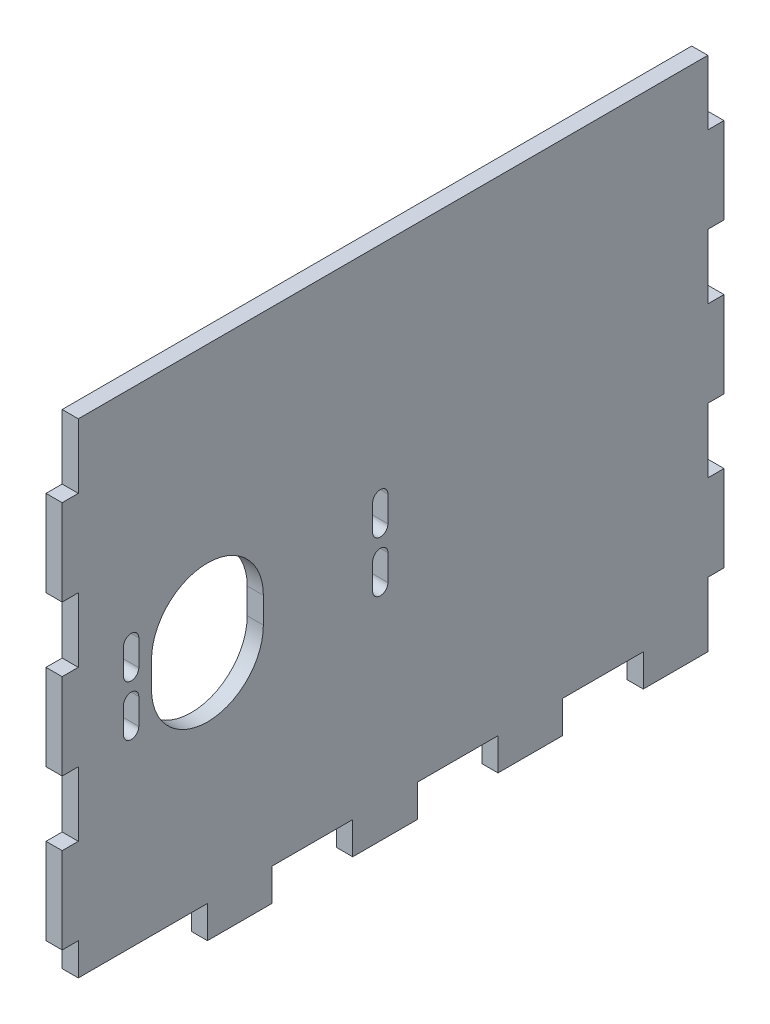
SolidWorks part; units mm, degrees
material "Acrylic (Medium-high impact)"
ref_plane "Front" through (0, 0, 0) normal (0, 0, 1) x (1, 0, 0)
ref_plane "Top" through (0, 0, 0) normal (0, 1, 0) x (1, 0, 0)
ref_plane "Right" through (0, 0, 0) normal (1, 0, 0) x (0, 0, -1)
sketch "Sketch1" plane through (0, 0, 0) normal (0, 0, 1) x (1, 0, 0)
  line L0 (0, 143.002) -> (0, -143.002) construction
  line L1 (-3.302, 133.858) -> (-3.302, -143.002)
  line L2 (-3.302, -143.002) -> (3.302, -143.002)
  line L3 (3.302, 143.002) -> (3.302, -143.002)
  line L4 (3.302, 143.002) -> (-16.256, 143.002)
  line L5 (-5.842, 136.398) -> (-16.256, 136.398)
  line L6 (-16.256, 143.002) -> (-16.256, 136.398)
  line L8 (-28.956, 155.448) -> (16.002, 155.448)
  line L9 (-28.956, 155.448) -> (-28.956, -149.352)
  line L10 (-28.956, -149.352) -> (16.002, -149.352)
  line L11 (16.002, 155.448) -> (16.002, -149.352)
  arc A0 (-3.302, 133.858) -> (-5.842, 136.398) centre (-5.842, 133.858) ccw
  point P2 (0, -143.002)
  point P11 (0, 0)
  dimension "D5" = 2.54
  dimension "D1" = 6.604
  dimension "D2" = 12.954
  dimension "D3" = 6.604
  dimension "D4" = 286.004
  dimension "D6" = 304.8
  dimension "D7" = 6.35
  dimension "D8" = 12.7
  dimension "D9" = 12.7
extrude "Boss-Extrude1" add sketch "Sketch1" along normal blind 3.175
sketch "Sketch2" plane through (16.002, 0, 0) normal (1, 0, 0) x (0, 0, -1)
  line L0 (-3.175, -149.352) -> (-3.175, 155.448) construction
  line L1 (-3.175, -47.752) -> (127, -47.752)
  line L2 (-3.175, -47.752) -> (-3.175, -149.352)
  line L3 (-3.175, -149.352) -> (127, -149.352)
  line L4 (127, -47.752) -> (127, -149.352)
  line L5 (14.4, -101.092) -> (14.4, -96.012)
  line L6 (36.4, -96.012) -> (36.4, -101.092)
  line L7 (8.4, -116.592) -> (8.4, -111.512)
  line L8 (11.4, -116.592) -> (11.4, -111.512)
  line L9 (8.4, -85.592) -> (8.4, -80.512)
  line L10 (11.4, -85.592) -> (11.4, -80.512)
  line L11 (25.4, -96.012) -> (25.4, -101.092) construction
  line L12 (42.4, -116.592) -> (42.4, -111.512)
  line L13 (39.4, -116.592) -> (39.4, -111.512)
  line L14 (39.4, -85.592) -> (39.4, -80.512)
  line L15 (42.4, -85.592) -> (42.4, -80.512)
  line L16 (0, -149.352) -> (0, 155.448) construction
  line L17 (125.4125, -60.452) -> (125.4125, -77.3853) construction
  line L18 (127, -47.752) -> (123.825, -47.752)
  line L19 (127, -47.752) -> (127, -60.452)
  line L20 (127, -60.452) -> (123.825, -60.452)
  line L21 (123.825, -47.752) -> (123.825, -60.452)
  line L22 (127, -107.0187) -> (123.825, -107.0187)
  line L23 (127, -107.0187) -> (127, -119.7187)
  line L24 (127, -119.7187) -> (123.825, -119.7187)
  line L25 (123.825, -107.0187) -> (123.825, -119.7187)
  line L26 (127, -136.652) -> (123.825, -136.652)
  line L27 (127, -136.652) -> (127, -149.352)
  line L28 (127, -149.352) -> (123.825, -149.352)
  line L29 (123.825, -136.652) -> (123.825, -149.352)
  line L30 (127, -77.3853) -> (123.825, -77.3853)
  line L31 (127, -77.3853) -> (127, -90.0853)
  line L32 (127, -90.0853) -> (123.825, -90.0853)
  line L33 (123.825, -77.3853) -> (123.825, -90.0853)
  line L34 (125.4125, -90.0853) -> (125.4125, -107.0187) construction
  line L35 (125.4125, -119.7187) -> (125.4125, -136.652) construction
  line L36 (10.4, -93.552) -> (59.4, -93.552) construction
  line L37 (59.4, -93.552) -> (59.4, -103.552) construction
  line L38 (59.4, -103.552) -> (10.4, -103.552) construction
  line L39 (10.4, -103.552) -> (10.4, -93.552) construction
  line L40 (8.9, -93.552) -> (8.9, -96.092)
  line L41 (11.9, -96.092) -> (11.9, -93.552)
  line L42 (11.9, -93.552) -> (11.9, -91.012)
  line L43 (8.9, -91.012) -> (8.9, -93.552)
  line L44 (8.9, -106.092) -> (8.9, -101.012)
  line L45 (11.9, -101.012) -> (11.9, -106.092)
  line L46 (60.9, -91.012) -> (60.9, -96.092)
  line L47 (57.9, -96.092) -> (57.9, -91.012)
  line L48 (60.9, -106.092) -> (60.9, -101.012)
  line L49 (57.9, -101.012) -> (57.9, -106.092)
  arc A0 (14.4, -101.092) -> (36.4, -101.092) centre (25.4, -101.092) ccw
  arc A1 (36.4, -96.012) -> (14.4, -96.012) centre (25.4, -96.012) ccw
  arc A2 (8.4, -116.592) -> (11.4, -116.592) centre (9.9, -116.592) ccw
  arc A3 (11.4, -111.512) -> (8.4, -111.512) centre (9.9, -111.512) ccw
  arc A4 (8.4, -85.592) -> (11.4, -85.592) centre (9.9, -85.592) ccw
  arc A5 (11.4, -80.512) -> (8.4, -80.512) centre (9.9, -80.512) ccw
  arc A6 (42.4, -116.592) -> (39.4, -116.592) centre (40.9, -116.592) cw
  arc A7 (39.4, -111.512) -> (42.4, -111.512) centre (40.9, -111.512) cw
  arc A8 (42.4, -85.592) -> (39.4, -85.592) centre (40.9, -85.592) cw
  arc A9 (39.4, -80.512) -> (42.4, -80.512) centre (40.9, -80.512) cw
  circle A10 centre (10.4, -93.552) radius 1.5
  circle A11 centre (59.4, -93.552) radius 1.5
  circle A12 centre (10.4, -103.552) radius 1.5
  circle A13 centre (59.4, -103.552) radius 1.5
  arc A14 (8.9, -96.092) -> (11.9, -96.092) centre (10.4, -96.092) ccw
  arc A15 (11.9, -91.012) -> (8.9, -91.012) centre (10.4, -91.012) ccw
  arc A16 (8.9, -101.012) -> (11.9, -101.012) centre (10.4, -101.012) cw
  arc A17 (11.9, -106.092) -> (8.9, -106.092) centre (10.4, -106.092) cw
  arc A18 (60.9, -96.092) -> (57.9, -96.092) centre (59.4, -96.092) cw
  arc A19 (57.9, -91.012) -> (60.9, -91.012) centre (59.4, -91.012) cw
  arc A20 (60.9, -101.012) -> (57.9, -101.012) centre (59.4, -101.012) ccw
  arc A21 (57.9, -106.092) -> (60.9, -106.092) centre (59.4, -106.092) ccw
  point P44 (25.4, -98.552)
  point P47 (-3.175, -98.552)
  point P71 (10.4, -98.552)
  point P72 (14.4, -98.552)
  point P103 (60.9, -93.552)
  point P105 (60.9, -103.552)
  point P106 (11.9, -103.552)
  line M17 (0, -149.352) -> (0, 155.448)
  line M19 (-3.175, 155.448) -> (-3.175, -149.352)
  line M20 (-3.175, -149.352) -> (0, -149.352)
  dimension "D1" = 22
  dimension "D6" = 1.5
  dimension "D10" = 1.5
  dimension "D18" = 3
  dimension "D2" = 5.08
  dimension "D3" = 5.08
  dimension "D4" = 15.5
  dimension "D5" = 15.5
  dimension "D7" = 15.5
  dimension "D8" = 15.5
  dimension "D9" = 5.08
  dimension "D11" = 25.4
  dimension "D12" = 50.8
  dimension "D13" = 101.6
  dimension "D14" = 12.7
  dimension "D15" = 3.175
  dimension "D16" = 10
  dimension "D17" = 49
  dimension "D19" = 5.08
  dimension "D20" = 5.08
  dimension "D21" = 15
extrude "Boss-Extrude2" add sketch "Sketch2" against normal blind 3.175 contours L33 L30 L4 L20 L21 L1 L3 L29 L26 L24 L25 L22 L32 A5 L10 A4 L9 A3 L8 A2 L7 A1 L6 A0 L5 L13 A7 L12 A6 L14 A9 L15 A8 M17 | L1 M19 M20 M17 | L10 A5 L9 A4 | A9 L14 A8 L15 | A7 L13 A6 L12 | L8 A3 L7 A2 region at (16.002, -98.552, -64.7183) region at (16.002, -98.552, 1.5875) region at (16.002, -114.052, -9.9) region at (16.002, -83.052, -9.9) region at (16.002, -114.052, -40.9) region at (16.002, -83.052, -40.9)
sketch "Sketch3" plane through (12.827, 0, 0) normal (-1, 0, 0) x (0, 0, 1)
  line L0 (-123.825, -136.652) -> (-123.825, -149.352) construction
  line L1 (-123.825, -143.002) -> (0, -143.002)
  line L2 (-123.825, -143.002) -> (-123.825, -149.352)
  line L3 (-123.825, -149.352) -> (0, -149.352)
  line L4 (0, -143.002) -> (0, -149.352)
  dimension "D1" = 6.35
extrude "Boss-Extrude3" add sketch "Sketch3" along normal up to surface (41.783 mm away) up to face at (-28.956, 3.048, 1.5875)
sketch "Sketch4" plane through (0, -149.352, 0) normal (0, -1, 0) x (1, 0, 0)
  line L0 (9.652, -25.4) -> (9.652, -38.1)
  line L1 (16.002, 3.175) -> (9.652, 3.175)
  line L2 (16.002, 3.175) -> (16.002, -9.525)
  line L3 (16.002, -9.525) -> (9.652, -9.525)
  line L4 (9.652, 3.175) -> (9.652, -9.525)
  line L5 (16.002, -25.4) -> (9.652, -25.4)
  line L6 (16.002, -25.4) -> (16.002, -38.1)
  line L7 (16.002, -38.1) -> (9.652, -38.1)
  line L8 (9.652, -53.975) -> (9.652, -66.675)
  line L9 (16.002, -53.975) -> (9.652, -53.975)
  line L10 (16.002, -53.975) -> (16.002, -66.675)
  line L11 (16.002, -66.675) -> (9.652, -66.675)
  line L12 (9.652, -82.55) -> (9.652, -95.25)
  line L13 (16.002, -82.55) -> (9.652, -82.55)
  line L14 (16.002, -82.55) -> (16.002, -95.25)
  line L15 (16.002, -95.25) -> (9.652, -95.25)
  line L16 (9.652, -111.125) -> (9.652, -123.825)
  line L17 (16.002, -111.125) -> (9.652, -111.125)
  line L18 (16.002, -111.125) -> (16.002, -123.825)
  line L19 (16.002, -123.825) -> (9.652, -123.825)
  line L36 (-6.477, 3.175) -> (-6.477, -123.825) construction
  line L37 (-28.956, 3.175) -> (16.002, 3.175) construction
  line L38 (-28.956, -123.825) -> (16.002, -123.825) construction
  line L39 (-22.606, 3.175) -> (-22.606, -123.825)
  line L40 (16.002, 3.175) -> (9.652, 3.175)
  line L41 (16.002, 3.175) -> (16.002, -123.825)
  line L42 (16.002, -123.825) -> (9.652, -123.825)
  line L43 (9.652, 3.175) -> (9.652, -123.825)
  line L44 (-28.956, -123.825) -> (-22.606, -123.825)
  line L45 (-28.956, 3.175) -> (-28.956, -123.825)
  line L46 (-28.956, 3.175) -> (-22.606, 3.175)
  line L47 (-28.956, -123.825) -> (-22.606, -123.825)
  line L48 (-28.956, -107.95) -> (-28.956, -123.825)
  line L49 (-28.956, -107.95) -> (-22.606, -107.95)
  line L50 (-22.606, -107.95) -> (-22.606, -123.825)
  line L51 (-28.956, -106.3625) -> (-22.606, -106.3625)
  line L52 (-28.956, -93.6625) -> (-28.956, -106.3625)
  line L53 (-28.956, -93.6625) -> (-22.606, -93.6625)
  line L54 (-22.606, -93.6625) -> (-22.606, -106.3625)
  line L55 (-28.956, -92.075) -> (-22.606, -92.075)
  line L56 (-28.956, -79.375) -> (-28.956, -92.075)
  line L57 (-28.956, -79.375) -> (-22.606, -79.375)
  line L58 (-22.606, -79.375) -> (-22.606, -92.075)
  line L59 (-28.956, -77.7875) -> (-22.606, -77.7875)
  line L60 (-28.956, -65.0875) -> (-28.956, -77.7875)
  line L61 (-28.956, -65.0875) -> (-22.606, -65.0875)
  line L62 (-22.606, -65.0875) -> (-22.606, -77.7875)
  line L63 (-28.956, -123.825) -> (-22.606, -123.825)
  line L64 (-28.956, -111.125) -> (-28.956, -123.825)
  line L65 (-28.956, -111.125) -> (-22.606, -111.125)
  line L66 (-22.606, -111.125) -> (-22.606, -123.825)
  line L67 (-28.956, -95.25) -> (-22.606, -95.25)
  line L68 (-28.956, -82.55) -> (-28.956, -95.25)
  line L69 (-28.956, -82.55) -> (-22.606, -82.55)
  line L70 (-22.606, -82.55) -> (-22.606, -95.25)
  line L71 (-28.956, -66.675) -> (-22.606, -66.675)
  line L72 (-28.956, -53.975) -> (-28.956, -66.675)
  line L73 (-28.956, -53.975) -> (-22.606, -53.975)
  line L74 (-22.606, -53.975) -> (-22.606, -66.675)
  line L75 (-28.956, -38.1) -> (-22.606, -38.1)
  line L76 (-28.956, -25.4) -> (-28.956, -38.1)
  line L77 (-28.956, -25.4) -> (-22.606, -25.4)
  line L78 (-22.606, 3.175) -> (-22.606, -9.525)
  line L79 (-28.956, -9.525) -> (-22.606, -9.525)
  line L80 (-28.956, 3.175) -> (-28.956, -9.525)
  line L81 (-28.956, 3.175) -> (-22.606, 3.175)
  line L82 (-22.606, -25.4) -> (-22.606, -38.1)
  line L83 (-16.129, 0.381) -> (-22.606, 0.381) construction
  line L85 (-28.956, 3.175) -> (-22.606, 3.175)
  line L86 (-28.956, 3.175) -> (-28.956, -2.413)
  line L87 (-28.956, -2.413) -> (-22.606, -2.413)
  line L88 (-22.606, 3.175) -> (-22.606, -2.413)
  line L92 (9.652, 3.175) -> (9.652, -2.413)
  line L93 (9.652, 3.175) -> (16.002, 3.175)
  line L94 (16.002, 3.175) -> (16.002, -2.413)
  line L95 (9.652, -2.413) -> (16.002, -2.413)
  line L96 (-28.956, 3.175) -> (16.002, 3.175)
  line L97 (-28.956, 3.175) -> (-28.956, -2.413)
  line L98 (-28.956, -2.413) -> (16.002, -2.413)
  line L99 (16.002, 3.175) -> (16.002, -2.413)
  line L100 (-9.652, 3.175) -> (-9.652, -2.413)
  line L101 (-9.652, -2.413) -> (-3.302, -2.413)
  line L102 (-3.302, 3.175) -> (-3.302, -2.413)
  line L103 (-9.652, 3.175) -> (-3.302, 3.175)
  line L104 (-9.779, -2.413) -> (-16.129, -2.413)
  line L105 (-9.779, -2.413) -> (-9.779, 3.175)
  line L106 (-9.779, 3.175) -> (-16.129, 3.175)
  line L107 (-16.129, -2.413) -> (-16.129, 3.175)
  line L108 (-9.779, 0.381) -> (-3.302, 0.381) construction
  line L109 (-3.302, 3.175) -> (-3.302, 0) construction
  line L111 (-28.956, 3.175) -> (16.002, 3.175)
  line L112 (-28.956, 3.175) -> (-28.956, -2.413)
  line L113 (-28.956, -2.413) -> (16.002, -2.413)
  line L114 (16.002, 3.175) -> (16.002, -2.413)
  line M38 (16.002, -123.825) -> (16.002, 3.175)
  line M39 (16.002, 3.175) -> (-28.956, 3.175)
  dimension "D1" = 6.35
  dimension "D2" = 12.7
  dimension "D4" = 5.588
  dimension "D5" = 6.35
  dimension "D7" = 6.35
  dimension "D3" = 5
  dimension "D6" = 3
sketch "Sketch6" plane through (0, 0, 3.175) normal (0, 0, 1) x (1, 0, 0)
  line L1 (16.002, -60.452) -> (12.827, -60.452)
  line L2 (16.002, -60.452) -> (16.002, -77.3853)
  line L3 (16.002, -77.3853) -> (12.827, -77.3853)
  line L4 (12.827, -60.452) -> (12.827, -77.3853)
  line L5 (16.002, -90.0853) -> (12.827, -90.0853)
  line L6 (16.002, -90.0853) -> (16.002, -107.0187)
  line L7 (16.002, -107.0187) -> (12.827, -107.0187)
  line L8 (12.827, -90.0853) -> (12.827, -107.0187)
  line L9 (16.002, -119.7187) -> (12.827, -119.7187)
  line L10 (16.002, -119.7187) -> (16.002, -136.652)
  line L11 (16.002, -136.652) -> (12.827, -136.652)
  line L12 (12.827, -119.7187) -> (12.827, -136.652)
  line L13 (-28.956, -149.352) -> (16.002, -149.352) construction
  line L14 (16.002, -47.752) -> (12.827, -47.752)
  line L15 (16.002, -47.752) -> (16.002, -149.352)
  line L16 (16.002, -149.352) -> (12.827, -149.352)
  line L17 (12.827, -47.752) -> (12.827, -149.352)
  line M1 (16.002, -149.352) -> (16.002, 155.448)
  line M4 (-28.956, -149.352) -> (16.002, -149.352)
sketch "Sketch7" plane through (16.002, 0, 0) normal (1, 0, 0) x (0, 0, -1)
  line L1 (-3.175, 180.723) -> (327.0227, 180.723)
  line L2 (-3.175, 180.723) -> (-3.175, -143.002)
  line L3 (-3.175, -143.002) -> (327.0227, -143.002)
  line L4 (327.0227, 180.723) -> (327.0227, -143.002)
  line L5 (-3.175, -149.352) -> (-3.175, 155.448) construction
  line L6 (123.825, -143.002) -> (0, -143.002) construction
  point P10 (161.9239, -143.002)
extrude "Cut-Extrude1" [suppressed] cut sketch "Sketch7" against normal through all
extrude "Cut-Extrude2" [suppressed] cut sketch "Sketch4" against normal blind 6.35
sketch "Sketch8" plane through (0, 0, 3.175) normal (0, 0, 1) x (1, 0, 0)
  line L0 (-28.956, -149.352) -> (16.002, -149.352) construction
  line L1 (12.827, -149.352) -> (-54.2235, -149.352)
  line L2 (12.827, -149.352) -> (12.827, 165.6994)
  line L3 (12.827, 165.6994) -> (-54.2235, 165.6994)
  line L4 (-54.2235, -149.352) -> (-54.2235, 165.6994)
  line L5 (12.827, -60.452) -> (12.827, -77.3853) construction
  line L7 (16.002, -47.752) -> (12.827, -47.752)
  line L8 (16.002, -47.752) -> (16.002, 165.6994)
  line L9 (16.002, 165.6994) -> (12.827, 165.6994)
  line L10 (12.827, -47.752) -> (12.827, 165.6994)
  line M6 (16.002, 155.448) -> (-28.956, 155.448)
  line M7 (-28.956, 155.448) -> (-28.956, -149.352)
  line M8 (-28.956, -149.352) -> (16.002, -149.352)
  line M9 (-16.256, 143.002) -> (3.302, 143.002)
  line M10 (3.302, 143.002) -> (3.302, -143.002)
  line M11 (3.302, -143.002) -> (-3.302, -143.002)
  line M12 (-3.302, -143.002) -> (-3.302, 133.858)
  arc M13 (-3.302, 133.858) -> (-5.842, 136.398) centre (-5.842, 133.858) ccw
  line M14 (-5.842, 136.398) -> (-16.256, 136.398)
  line M15 (-16.256, 136.398) -> (-16.256, 143.002)
extrude "Cut-Extrude4" cut sketch "Sketch8" against normal through all and the other way through all contours L2 M8 M6 M7 M15 M9 M10 M11 M12 M13 M14 | L4 L1 L2 L3 M7 M6 | L10 L7 L8 L9 region at (-9.4671, 2.4795, 3.175) region at (-39.878, 15.9551, 3.175)
extrude "Cut-Extrude5" cut sketch "Sketch6" against normal blind 3.175 contours L14 L17 L1 M1 | L3 L17 L5 M1 | L7 L17 L9 M1 | L11 L17 M4 M1 region at (14.4145, -54.102, 3.175) region at (14.4145, -83.7353, 3.175) region at (14.4145, -113.3687, 3.175) region at (14.4145, -143.002, 3.175)
extrude "Cut-Extrude6" cut sketch "Sketch4<3>" against normal blind 6.35 contours L15 L43 L17 M38 | L11 L43 L13 M38 | L7 L43 L9 M38 | L3 L43 L5 M38 | L4 L95 L41 M39 | L95 L43 L3 M38 region at (12.827, -149.352, -17.4625) region at (12.827, -149.352, -46.0375) region at (12.827, -149.352, -5.969) region at (12.827, -149.352, 0.381) region at (12.827, -149.352, -74.6125) region at (12.827, -149.352, -103.1875)
sketch "Sketch4<3>" plane through (0, -149.352, 0) normal (0, -1, 0) x (1, 0, 0) same geometry as "Sketch4"
equation "\"bottomThickness\"= .25in"
equation "\"wallThickness\"= .125in"
equation "\"D1@Boss-Extrude1\"=\"wallThickness\""
equation "\"D1@Boss-Extrude2\"=\"wallThickness\""
equation "\"D15@Sketch2\"=\"wallThickness\""
equation "\"D1@Sketch3\"=\"bottomThickness\""
equation "\"D1@Cut-Extrude6\"=\"bottomThickness\""
equation "\"D1@Cut-Extrude5\"=\"wallThickness\""
